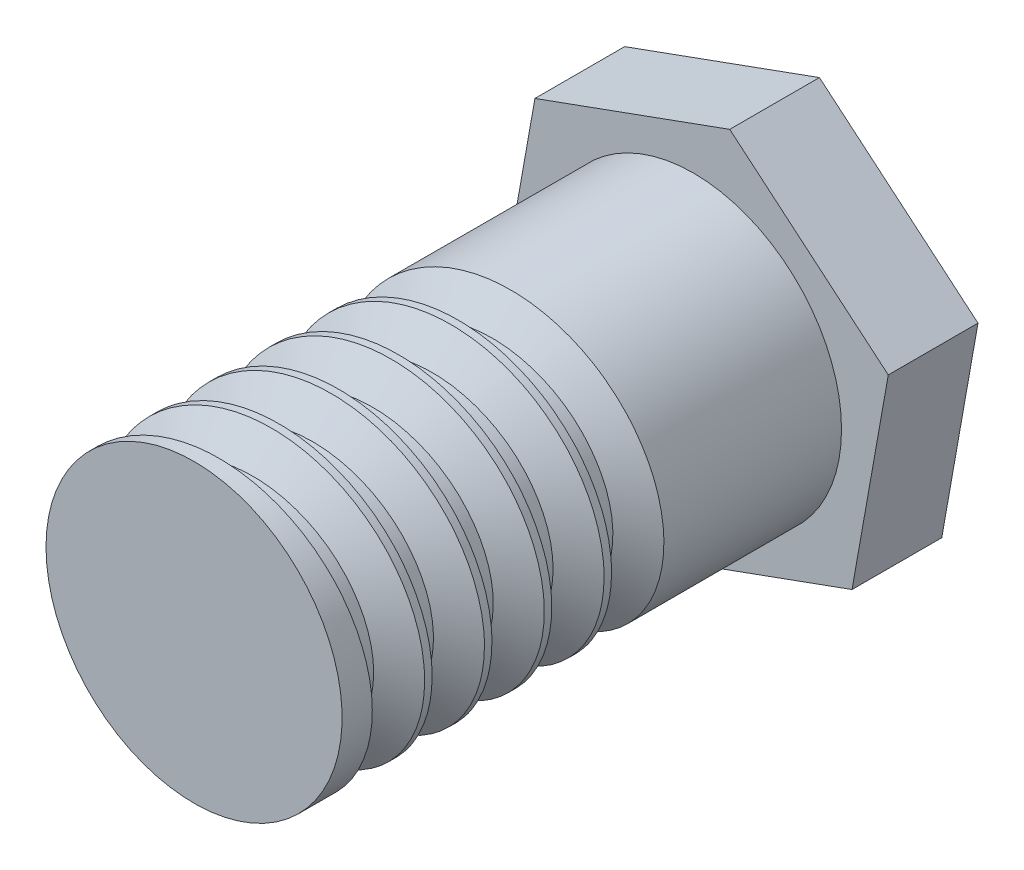
SolidWorks part; units mm, degrees
ref_plane "Front Plane" through (0, 0, 0) normal (0, 0, 1) x (1, 0, 0)
ref_plane "Top Plane" through (0, 0, 0) normal (0, 1, 0) x (1, 0, 0)
ref_plane "Right Plane" through (0, 0, 0) normal (1, 0, 0) x (0, 0, -1)
sketch "Sketch1" plane through (0, 0, 0) normal (0, 0, 1) x (1, 0, 0)
  line L1 (1.2119, 6.8214) -> (-5.3015, 4.4602)
  line L2 (-5.3015, 4.4602) -> (-6.5135, -2.3611)
  line L3 (-6.5135, -2.3611) -> (-1.2119, -6.8214)
  line L4 (-1.2119, -6.8214) -> (5.3015, -4.4602)
  line L5 (5.3015, -4.4602) -> (6.5135, 2.3611)
  line L6 (6.5135, 2.3611) -> (1.2119, 6.8214)
  circle A0 centre (0, 0) radius 6 construction
  dimension "D1" = 12
extrude "Boss-Extrude1" add sketch "Sketch1" along normal blind 3
sketch "Sketch2" plane through (0, 0, 3) normal (0, 0, 1) x (1, 0, 0)
  circle A0 centre (0, 0) radius 4.95
  dimension "D1" = 9.9
extrude "Boss-Extrude2" add sketch "Sketch2" along normal blind 16.7
thread "Thread1" pitch 2 method cut profile "Thread Profile1" start angle 0, offset 0, length 10, pitch 2, diameter 9.9
ref_plane "Plane1" through (-4.95, 0, 19.7) normal (0, -1, 0) x (-1, 0, 0)
sketch "Thread Profile1" plane through (-4.95, 0, 19.7) normal (0, -1, 0) x (-1, 0, 0)
  line L0 (0, 0) -> (0, 2) construction
  line L11 (0, 0) -> (0, 1.75)
  line L12 (0, 1.75) -> (-1.0825, 1.125)
  line L13 (-1.0825, 1.125) -> (-1.0825, 0.625)
  line L15 (-1.0825, 0.625) -> (0, 0)
  line L17 (-1.0825, 0.875) -> (0, 0.875) construction
  point P2 (0, 0)
  dimension "Pitch" = 2
  dimension "Profile_Angle" = 60
  dimension "Profile_Land" = 0.5
  dimension "Profile_Height" = 1.0825
